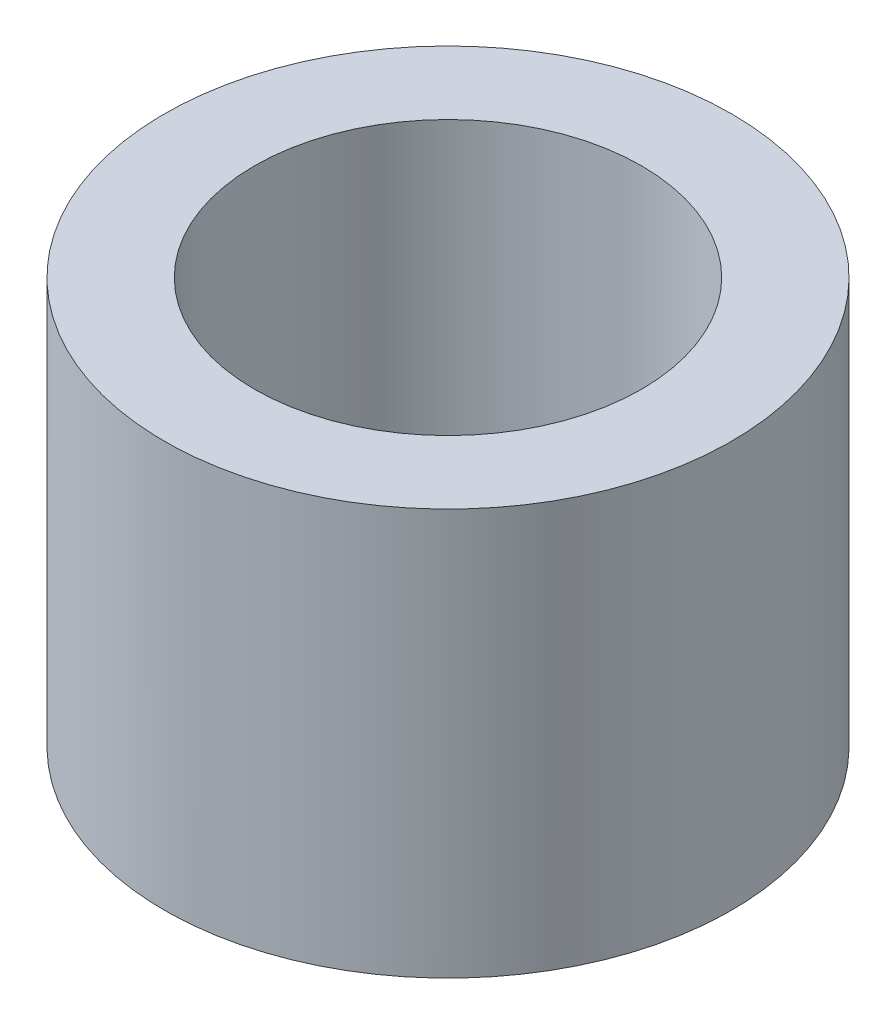
SolidWorks part; units mm, degrees
ref_plane "Front Plane" through (0, 0, 0) normal (0, 0, 1) x (1, 0, 0)
ref_plane "Top Plane" through (0, 0, 0) normal (0, 1, 0) x (1, 0, 0)
ref_plane "Right Plane" through (0, 0, 0) normal (1, 0, 0) x (0, 0, -1)
sketch "Sketch1" plane through (0, 0, 0) normal (0, 1, 0) x (1, 0, 0)
  circle A0 centre (0, 0) radius 8.001
  circle A1 centre (0, 0) radius 5.461
  dimension "D1" = 16.002
  dimension "D2" = 10.922
extrude "Boss-Extrude1" add sketch "Sketch1" along normal blind 11.461 contours A1 | A0 A1 region at (-7.7747, 0, 0) region at (0, 0, 0)
sketch "Sketch2" plane through (0, 0, 0) normal (0, 0, 1) x (1, 0, 0)
  line L0 (0, 0) -> (0, -2.54)
  line L1 (0, -2.54) -> (8.001, 0)
  line L2 (8.001, 0) -> (0, 0)
  dimension "D1" = 2.54
revolve "Revolve1" add sketch "Sketch2" angle 360 about L0
extrude "Cut-Extrude1" cut sketch "Sketch1<6>" against normal blind 9.46 from surface contours A1 region at (0, 0, 0) starting at face at (0, 11.461, 8.001)
sketch "Sketch1<6>" plane through (0, 0, 0) normal (0, 1, 0) x (1, 0, 0) same geometry as "Sketch1"
equation "\"OldSchoolLengthHoles\"= 2.5in'OldSchool > NewSchool"
equation "\"SchoolWidthHoles\"= 1.625in'OldSchool = NewSchool"
equation "\"Angle\"= 40deg'Looks about <= 40deg"
equation "\"Width\"= 2.125in'Pretty sure this is standardized on longboard and skateboard"
equation "\"Length\"= 3in'Will have some variation?"
equation "\"NewSchoolLengthHoles\"= 2.125in'NewSchool Mounting"
equation "\"HoleSize\"= ( 3in / 16 )'hole"
equation "\"Depth\"= 1in / 8'Assuming same depth as a riserplate"
equation "\"KingpinBoltSize\"= 3in / 8"
equation "\"PivotCupDia\"= 0.63in'0.7in (large) 0.626 (small)"
equation "\"PivotCupDepth\"= 12mm'15mm (large) 12mm (small)"
equation "\"PivotCupEndAngle\"= 18deg'Don't Know looks like (I don't even think I used this)"
equation "\"PivotCupInnerDia\"= 0.43in'0.5in (large) 0.43 (small)"
equation "\"D1@Sketch1\"=\"PivotCupDia\""
equation "\"D2@Sketch1\"=\"PivotCupInnerDia\""
equation "\"D1@Boss-Extrude1\"=\"PivotCupDepth\"-(\"PivotCupDepth\"-\"PivotCupInnerDia\")/2"
equation "\"D3\"= 90 - \"PivotCupEndAngle\""
equation "\"D1@Sketch2\"=(\"PivotCupDia\"-\"PivotCupInnerDia\")/2"
equation "\"D1@Cut-Extrude1\"=\"PivotCupDepth\"-(\"PivotCupDia\"-\"PivotCupInnerDia\")/2"
